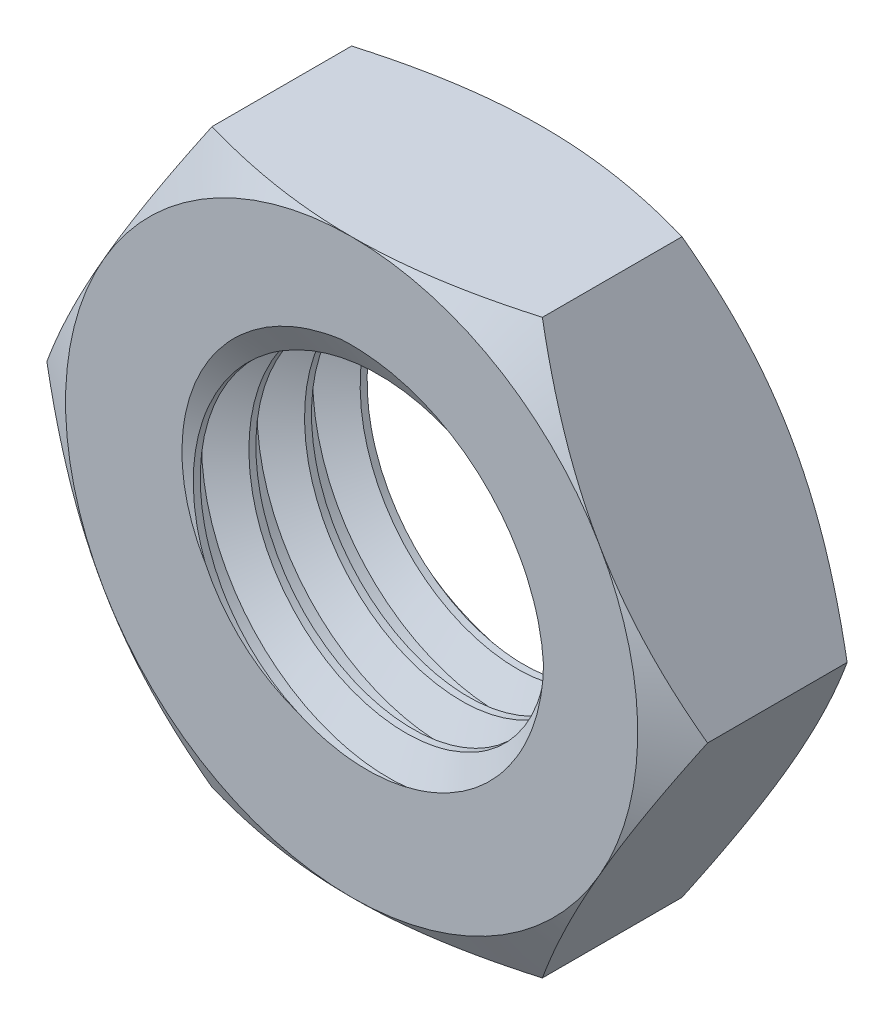
SolidWorks part; units mm, degrees
ref_plane "Front Plane" through (0, 0, 0) normal (0, 0, 1) x (1, 0, 0)
ref_plane "Top Plane" through (0, 0, 0) normal (0, 1, 0) x (1, 0, 0)
ref_plane "Right Plane" through (0, 0, 0) normal (1, 0, 0) x (0, 0, -1)
sketch "Sketch1" plane through (0, 0, 0) normal (0, 0, 1) x (1, 0, 0)
  line L1 (5.1962, 9) -> (-5.1962, 9)
  line L2 (-5.1962, 9) -> (-10.3923, 0)
  line L3 (-10.3923, 0) -> (-5.1962, -9)
  line L4 (-5.1962, -9) -> (5.1962, -9)
  line L5 (5.1962, -9) -> (10.3923, 0)
  line L6 (10.3923, 0) -> (5.1962, 9)
  circle A0 centre (0, 0) radius 9 construction
  dimension "D1" = 18
extrude "Boss-Extrude1" add sketch "Sketch1" along normal blind 6
sketch "Sketch3" plane through (0, 0, 0) normal (1, 0, 0) x (0, 0, -1)
  line L0 (0, 9) -> (0, 11.8226)
  line L1 (0, 11.8226) -> (-1.6297, 11.8226)
  line L2 (-1.6297, 11.8226) -> (0, 9)
  line L3 (0, 0) -> (50000, 0) construction
  dimension "D1" = 30
revolve "Cut-Revolve1" cut sketch "Sketch3" angle 360 about L3
ref_plane "Plane1" through (0, 0, 3) normal (0, 0, -1) x (-1, 0, 0)
mirror "Mirror1" about plane through (0, 0, 3) normal (0, 0, -1) of "Cut-Revolve1"
hole_wizard "M12x1.75 Tapped Hole1" positions "Sketch6" profile "Sketch7" tap size "M12x1.75" standard "ANSI Metric" end condition through all
sketch "Sketch6" plane through (0, 0, 0) normal (0, 0, -1) x (-1, 0, 0)
  point P0 (0, 0)
sketch "Sketch7" plane through (0, 0, 0) normal (1, 0, 0) x (0, 1, 0)
  line L0 (0, 0) -> (0, 6)
  line L1 (0, 6) -> (5.1, 6)
  line L2 (5.1, 6) -> (5.1, 0)
  line L5 (5.1, 0) -> (0, 0)
  line L11 (0, -6.35) -> (0, 107.95) construction
  dimension "Thru Tap Drill Dia." = 10.2
  dimension "Thru Tap Drill Depth" = 6
cosmetic thread "Hole Thread1" parameters "D2"=12
thread "Thread1" pitch 1.75 method cut profile "Thread Profile1" start angle 0, offset 2, length 20, pitch 1.75, diameter 10.2
ref_plane "Plane2" through (5.1, 0, -2) normal (0, 1, 0) x (-1, 0, 0)
sketch "Thread Profile1" plane through (5.1, 0, -2) normal (0, 1, 0) x (-1, 0, 0)
  line L0 (0, 0) -> (0, 1.75) construction
  line L11 (0, 0) -> (0, 1.5312)
  line L12 (0, 1.5312) -> (-0.9472, 0.9844)
  line L13 (-0.9472, 0.9844) -> (-0.9472, 0.5469)
  line L15 (-0.9472, 0.5469) -> (0, 0)
  line L17 (-0.9472, 0.7656) -> (0, 0.7656) construction
  point P2 (0, 0)
  dimension "Pitch" = 1.75
  dimension "Profile_Angle" = 60
  dimension "Profile_Land" = 0.4375
  dimension "Profile_Height" = 0.9472
